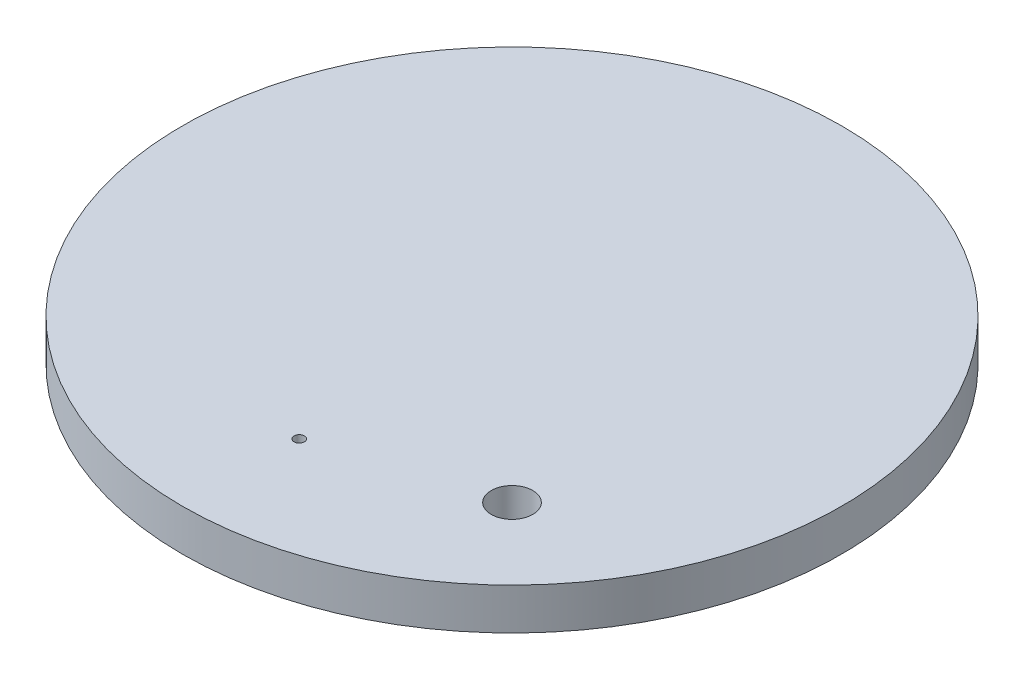
SolidWorks part; units mm, degrees
material "1060 Alloy"
ref_plane "Front Plane" through (0, 0, 0) normal (0, 0, 1) x (1, 0, 0)
ref_plane "Top Plane" through (0, 0, 0) normal (0, 1, 0) x (1, 0, 0)
ref_plane "Right Plane" through (0, 0, 0) normal (1, 0, 0) x (0, 0, -1)
sketch "Sketch1" plane through (0, 0, 0) normal (0, 1, 0) x (1, 0, 0)
  circle A0 centre (0, 0) radius 15.875
  dimension "D1" = 31.75
extrude "Boss-Extrude1" add sketch "Sketch1" along normal blind 1
sketch "Sketch2" plane through (0, 0, 0) normal (0, -1, 0) x (1, 0, 0)
  circle A0 centre (0, 0) radius 15.875
  circle A1 centre (0, 0) radius 9.525
  circle A2 centre (0, 0) radius 15.875 construction
  dimension "D1" = 0
  dimension "D2" = 19.05
extrude "Boss-Extrude2" add sketch "Sketch2" along normal blind 1
thread "Thread1" pitch 0.25 method cut profile "Thread Profile1" start angle 0, offset 0, length 1, pitch 0.25, diameter 19.05
ref_plane "Plane1" through (9.525, -1, 0) normal (0, 0, 1) x (1, 0, 0)
sketch "Thread Profile1" plane through (9.525, -1, 0) normal (0, 0, 1) x (1, 0, 0)
  line L0 (0, 0) -> (0, 0.25) construction
  line L1 (0, 0) -> (0.1353, 0.0781)
  line L2 (0.1353, 0.0781) -> (0.1353, 0.1094)
  line L3 (0.1353, 0.1094) -> (0, 0.1875)
  line L4 (0.1353, 0.0937) -> (0, 0.0937) construction
  line L11 (0, 0) -> (0, 0.1875)
  point P2 (0, 0)
  dimension "Pitch" = 0.25
  dimension "Profile_Angle" = 60
  dimension "Profile_Land" = 0.0312
  dimension "Profile_Height" = 0.1353
sketch "Sketch3" plane through (0, 1, 0) normal (0, 1, 0) x (1, 0, 0)
  circle A0 centre (0, -10.25) radius 0.25
  circle A1 centre (0, 0) radius 9.8
  dimension "D1" = 0.5
  dimension "D2" = 10.25
  dimension "D3" = 19.6
extrude "Cut-Extrude1" cut sketch "Sketch3" against normal through all both and the other way through all contours A1 A0 region at (0, 1, 10.25)
sketch "Sketch4" plane through (0, -1, 0) normal (0, -1, 0) x (1, 0, 0)
  line L0 (0, 0) -> (13.2597, 13.2597) construction
  circle A0 centre (7.7782, 7.7782) radius 1
  dimension "D2" = 2
  dimension "D1" = 11
extrude "Cut-Extrude2" cut sketch "Sketch4" against normal through all both and the other way through all
